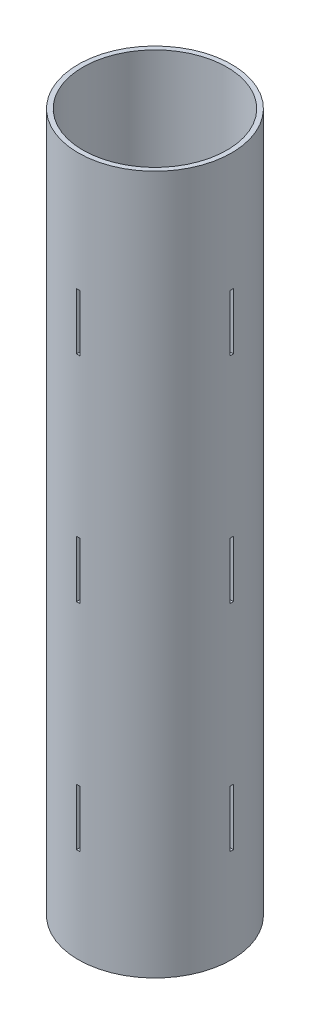
SolidWorks part; units mm, degrees
ref_plane "Front Plane" through (0, 0, 0) normal (0, 0, 1) x (1, 0, 0)
ref_plane "Top Plane" through (0, 0, 0) normal (0, 1, 0) x (1, 0, 0)
ref_plane "Right Plane" through (0, 0, 0) normal (1, 0, 0) x (0, 0, -1)
sketch "Sketch1" plane through (0, 0, 0) normal (0, 1, 0) x (1, 0, 0)
  circle A0 centre (0, 0) radius 32.5
  circle A1 centre (0, 0) radius 30.5
  dimension "D1" = 65
  dimension "D2" = 61
extrude "Boss-Extrude1" add sketch "Sketch1" along normal blind 296
sketch "Sketch2" plane through (0, 0, 0) normal (1, 0, 0) x (0, 0, -1)
  line L1 (0.75, 245.8798) -> (-0.75, 245.8798)
  line L2 (0.75, 245.8798) -> (0.75, 221.8798)
  line L3 (0.75, 221.8798) -> (-0.75, 221.8798)
  line L4 (-0.75, 245.8798) -> (-0.75, 221.8798)
  line L5 (0.75, 155) -> (-0.75, 155)
  line L6 (0.75, 155) -> (0.75, 131)
  line L7 (0.75, 131) -> (-0.75, 131)
  line L8 (-0.75, 155) -> (-0.75, 131)
  line L9 (0.75, 64) -> (-0.75, 64)
  line L10 (0.75, 64) -> (0.75, 40)
  line L11 (0.75, 40) -> (-0.75, 40)
  line L12 (-0.75, 64) -> (-0.75, 40)
extrude "Cut-Extrude1" cut sketch "Sketch2" against normal mid plane 100
sketch "Sketch3" plane through (0, 0, 0) normal (0, 0, 1) x (1, 0, 0)
  line L0 (0, 307.1688) -> (0, 342.7691) construction
  line L1 (-30.4908, 40) -> (-7.7248, 40) construction
  line L2 (-30.4908, 131) -> (-8.527, 131) construction
  line L3 (-30.4908, 221.8798) -> (-7.3578, 221.8798) construction
  line L5 (-0.75, 221.8798) -> (0.75, 221.8798)
  line L6 (-0.75, 221.8798) -> (-0.75, 245.8798)
  line L7 (-0.75, 245.8798) -> (0.75, 245.8798)
  line L8 (0.75, 221.8798) -> (0.75, 245.8798)
  line L9 (-0.75, 131) -> (0.75, 131)
  line L10 (-0.75, 131) -> (-0.75, 155)
  line L11 (-0.75, 155) -> (0.75, 155)
  line L12 (0.75, 131) -> (0.75, 155)
  line L13 (-0.75, 40) -> (0.75, 40)
  line L14 (-0.75, 40) -> (-0.75, 64)
  line L15 (-0.75, 64) -> (0.75, 64)
  line L16 (0.75, 40) -> (0.75, 64)
  dimension "D1" = 0.75
  dimension "D2" = 0.75
  dimension "D3" = 24
  dimension "D4" = 0.75
  dimension "D5" = 0.75
  dimension "D6" = 24
  dimension "D7" = 0.75
  dimension "D8" = 0.75
  dimension "D9" = 24
extrude "Cut-Extrude2" cut sketch "Sketch3" against normal mid plane 100
